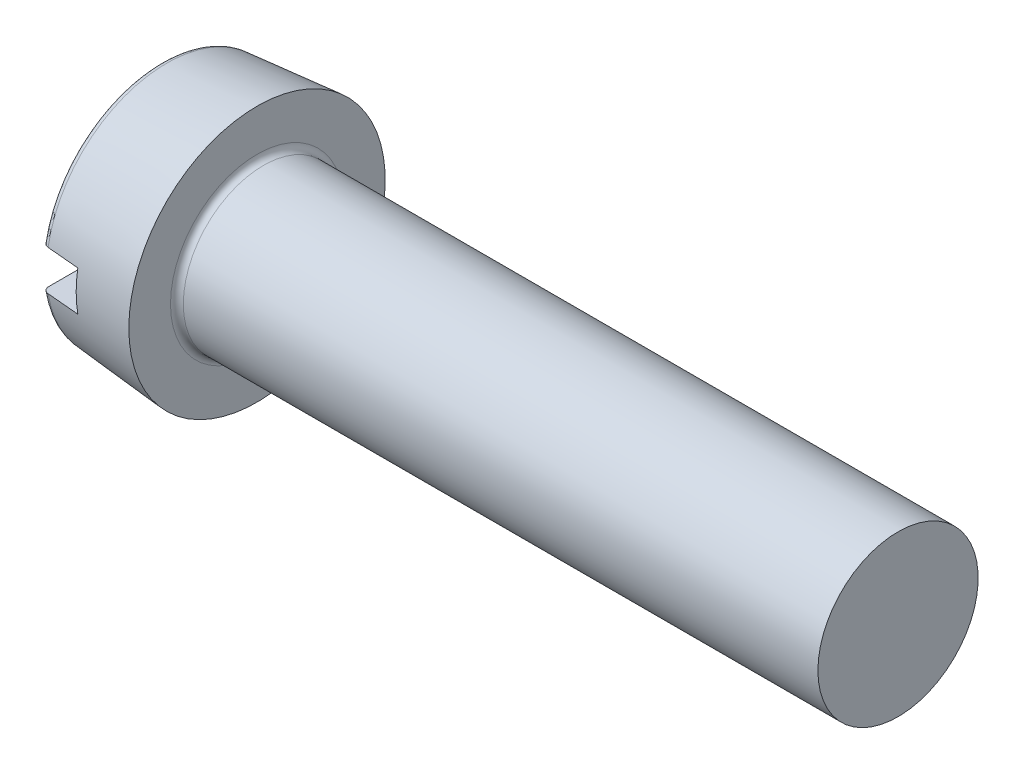
SolidWorks part; units mm, degrees
ref_plane "Front Plane" through (0, 0, 0) normal (0, 0, 1) x (1, 0, 0)
ref_plane "Top Plane" through (0, 0, 0) normal (0, 1, 0) x (1, 0, 0)
ref_plane "Right Plane" through (0, 0, 0) normal (1, 0, 0) x (0, 0, -1)
sketch "BodySke" plane through (0, 0, 0) normal (0, 0, 1) x (1, 0, 0)
  line L0 (0, 0) -> (154.7091, 0) construction
  line L1 (0, 0) -> (0, 7.4751)
  line L2 (0, 7.4751) -> (6, 8)
  line L3 (6, 8) -> (6, 5)
  line L4 (6, 5) -> (46, 5)
  line L5 (46, 5) -> (46, 0)
  line L6 (46, 0) -> (0, 0)
  line L7 (6, 0) -> (6, 8) construction
  line L8 (7.5, 0) -> (7.5, 8) construction
  point P12 (0, 4.172)
  dimension "Thread_length" = 40
  dimension "Thread_minor" = 8.344
  dimension "Advance" = 1.5
revolve "BaseBody" add sketch "BodySke" angle 360 about L0
cosmetic thread "ThreadCosmetic" [suppressed] parameters "Thread_length"=40, "Thread_minor"=8.344
fillet "Fillet1" radius 0.4 1 edges at (6, 0, 5)
fillet "Fillet2" radius 0.4 1 edges at (0, 0, 7.4751)
sketch "SlotSke" plane through (0, 0, 0) normal (-1, 0, 0) x (0, 0, 1)
  line L0 (8, -1.25) -> (-8, 1.25) construction
  line L1 (-8, 1.25) -> (8, 1.25)
  line L2 (-8, 1.25) -> (-8, -1.25)
  line L3 (-8, -1.25) -> (8, -1.25)
  line L4 (8, 1.25) -> (8, -1.25)
  dimension "D1" = 16
extrude "Slot" cut sketch "SlotSke" against normal blind 2.4
sketch "ThdSchSke" plane through (0, 0, 0) normal (0, 0, 1) x (1, 0, 0)
  line L0 (0, 0) -> (51.3012, 0) construction
  line L1 (45.522, 5) -> (45.522, 5.9561)
  line L2 (45.522, 5.9561) -> (46.478, 5.9561)
  line L3 (46.478, 5.9561) -> (46.478, 5)
  line L4 (46.478, 5) -> (46, 4.172)
  line L5 (46, 4.172) -> (45.522, 5)
  line L6 (46, 5) -> (46, 0) construction
  line L7 (6, 5) -> (46, 5) construction
revolve "ThreadSchematic" [suppressed] cut sketch "ThdSchSke" angle 360 about L0
pattern_linear "ThdSchPat" [suppressed] of bodies 115
equation "\"Thread_length@ThreadCosmetic\" = \"Thread_length@BodySke\""
equation "\"Thread_minor@ThreadCosmetic\" = \"Thread_minor@BodySke\""
equation "\"D1@SlotSke\" = \"Head_diameter@BodySke\""
equation "\"Advance@ThdSchPat\" = \"Advance@BodySke\""
equation "\"Tooth_Num@ThdSchPat\" =  int( \"Thread_length@BodySke\" / \"Advance@BodySke\" )"
